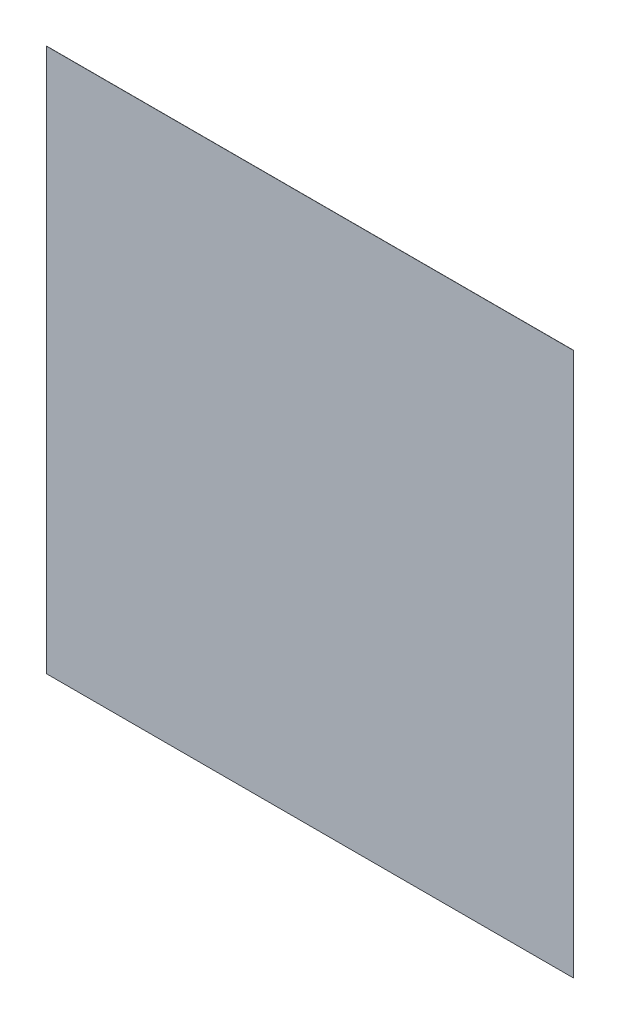
SolidWorks part; units mm, degrees
ref_plane "前视基准面" through (0, 0, 0) normal (0, 0, 1) x (1, 0, 0)
ref_plane "上视基准面" through (0, 0, 0) normal (0, 1, 0) x (1, 0, 0)
ref_plane "右视基准面" through (0, 0, 0) normal (1, 0, 0) x (0, 0, -1)
sketch "草图1" plane through (0, 0, 0) normal (0, 0, 1) x (1, 0, 0)
  line L1 (-160, 165) -> (160, 165)
  line L2 (-160, 165) -> (-160, -165)
  line L3 (-160, -165) -> (160, -165)
  line L4 (160, 165) -> (160, -165)
  line L5 (-160, 165) -> (160, -165) construction
  line L6 (-160, -165) -> (160, 165) construction
  point P0 (0, 0)
  dimension "D1" = 320
  dimension "D2" = 330
extrude "凸台-拉伸1" add sketch "草图1" along normal blind 0.1
